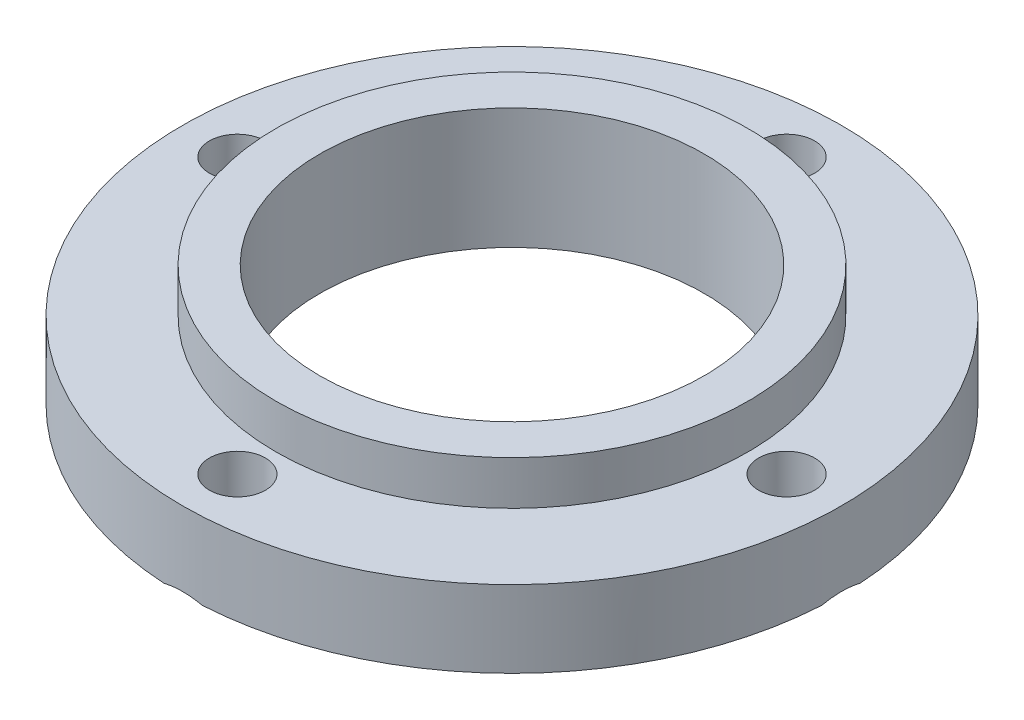
SolidWorks part; units mm, degrees
material "201 Annealed Stainless Steel (SS)"
ref_plane "Front" through (0, 0, 0) normal (0, 0, 1) x (1, 0, 0)
ref_plane "Top" through (0, 0, 0) normal (0, 1, 0) x (1, 0, 0)
ref_plane "Right" through (0, 0, 0) normal (1, 0, 0) x (0, 0, -1)
sketch "Sketch1" plane through (0, 0, 0) normal (0, 1, 0) x (1, 0, 0)
  circle A0 centre (0, 0) radius 30
  circle A1 centre (0, 0) radius 17.5
  dimension "D1" = 60
  dimension "D2" = 35
extrude "Boss-Extrude1" add sketch "Sketch1" along normal blind 7
sketch "Sketch2" plane through (0, 7, 0) normal (0, 1, 0) x (1, 0, 0)
  circle A0 centre (0, 0) radius 21.5
  circle A1 centre (0, 0) radius 17.5
  circle A3 centre (0, 0) radius 17.5 construction
  dimension "D1" = 4
extrude "Boss-Extrude2" add sketch "Sketch2" along normal blind 4
sketch "Sketch4" plane through (0, 0, 0) normal (0, -1, 0) x (1, 0, 0)
  circle A0 centre (25, 0) radius 2.55
  dimension "D1" = 5.1
  dimension "D2" = 25
extrude "Cut-Extrude1" cut sketch "Sketch4" against normal through all
chamfer "Chamfer1" distance 2.7 angle 45 1 edges at (25, 0, -2.55)
pattern_circular "CirPattern1" count 4 every 90 about axis through (0, 0, 0) along (0, 1, 0) of "Cut-Extrude1", "Chamfer1"
